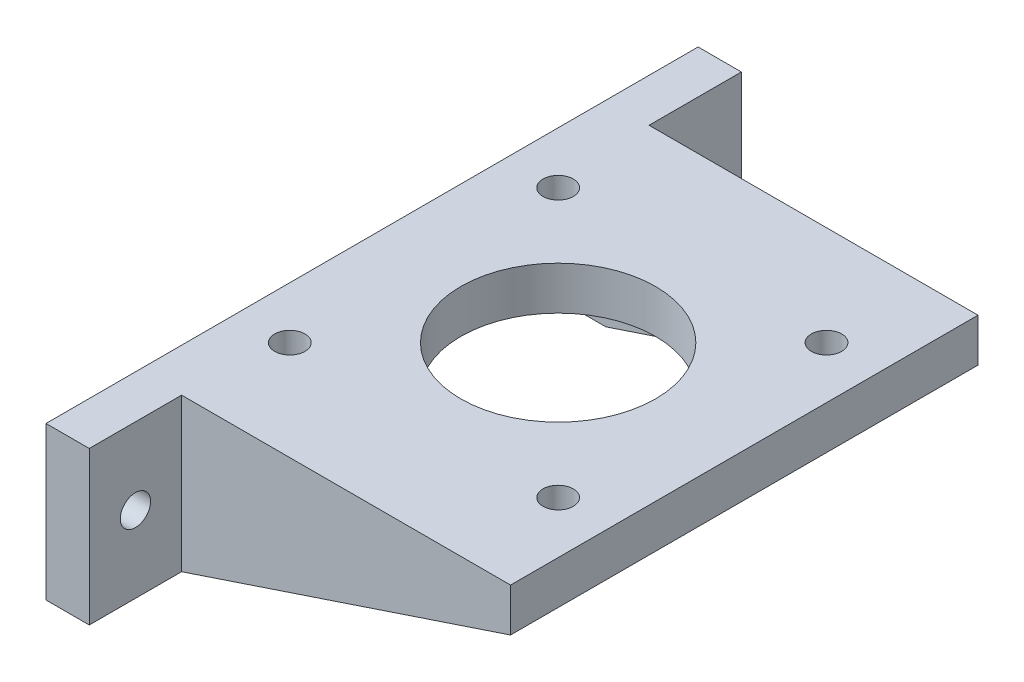
SolidWorks part; units mm, degrees
material "ABS"
ref_plane "Front Plane" through (0, 0, 0) normal (0, 0, 1) x (1, 0, 0)
ref_plane "Top Plane" through (0, 0, 0) normal (0, 1, 0) x (1, 0, 0)
ref_plane "Right Plane" through (0, 0, 0) normal (1, 0, 0) x (0, 0, -1)
sketch "Sketch1" plane through (0, 0, 0) normal (0, 0, 1) x (1, 0, 0)
  line L0 (5, 5) -> (43, 5)
  line L1 (0, 0) -> (5, 0)
  line L2 (0, 0) -> (0, 5)
  line L3 (0, 5) -> (5, 5)
  line L4 (5, 0) -> (5, 5)
  line L5 (43, 5) -> (43, 0)
  line L6 (43, 0) -> (5, 0)
  line L7 (5, 0) -> (5, -12.666)
  line L8 (5, -12.666) -> (0, -12.666)
  line L9 (0, -12.666) -> (0, 0)
  line L10 (5, -12.666) -> (43, 0)
  dimension "D1" = 5
  dimension "D2" = 5
  dimension "D3" = 43
  dimension "D4" = 12.666
extrude "Boss-Extrude1" add sketch "Sketch1" against normal blind 44 contours L1 L4 L3 L2 | L6 L5 L0 L4 region at (2.5, 2.5, 0) region at (24, 2.5, 0)
sketch "Sketch2" plane through (0, 5, 0) normal (0, 1, 0) x (1, 0, 0)
  line L3 (0, 44) -> (0, 0) construction
  line L4 (0, 0) -> (43, 0) construction
  circle A0 centre (21.5, 22) radius 11.25
  circle A1 centre (37, 37.5) radius 1.75
  circle A2 centre (6, 37.5) radius 1.75
  circle A3 centre (6, 6.5) radius 1.75
  circle A4 centre (37, 6.5) radius 1.75
  dimension "D3" = 22.5
  dimension "D4" = 3.5
  dimension "D1" = 21.5
  dimension "D2" = 22
  dimension "D5" = 15.5
  dimension "D6" = 15.5
  dimension "D7" = 2
  dimension "D8" = 2
extrude "Cut-Extrude1" cut sketch "Sketch2" against normal through all
extrude "Boss-Extrude2" add sketch "Sketch1<3>" along normal blind 5 contours L7 L10 L6 | L6 L5 L0 L4 | L1 L4 L3 L2 | L9 L8 L7 L1 region at (2.5, 2.5, 0) region at (24, 2.5, 0) region at (2.5, -6.333, 0) region at (17.6667, -4.222, 0)
sketch "Sketch1<3>" plane through (0, 0, 0) normal (0, 0, 1) x (1, 0, 0) same geometry as "Sketch1"
extrude "Boss-Extrude3" add sketch "Sketch1<4>" against normal blind 5 from vertex contours L1 L4 L3 L2 | L9 L8 L7 L1 | L7 L10 L6 | L6 L5 L0 L4 region at (2.5, 2.5, 0) region at (24, 2.5, 0) region at (2.5, -6.333, 0) region at (17.6667, -4.222, 0) starting at point (0, 5, -44)
sketch "Sketch1<4>" plane through (0, 0, 0) normal (0, 0, 1) x (1, 0, 0) same geometry as "Sketch1"
sketch "Sketch3" plane through (0, 0, 0) normal (-1, 0, 0) x (0, 0, 1)
  line L0 (5, -12.666) -> (0, -12.666) construction
  line L1 (5, 5) -> (15.666, 5)
  line L2 (5, 5) -> (5, -12.666)
  line L3 (5, -12.666) -> (15.666, -12.666)
  line L4 (15.666, 5) -> (15.666, -12.666)
  line L5 (10.333, 5) -> (10.333, -12.666) construction
  line L6 (15.666, -3.833) -> (5, -3.833) construction
  line L7 (-22, 5) -> (-22, 0) construction
  line L8 (-49, 5) -> (5, 5) construction
  line L9 (-44, 0) -> (0, 0) construction
  line L10 (-49, -12.666) -> (-59.666, -12.666)
  line L11 (-59.666, 5) -> (-59.666, -12.666)
  line L12 (-54.333, 5) -> (-54.333, -12.666) construction
  line L13 (-59.666, -3.833) -> (-49, -3.833) construction
  line L14 (-49, 5) -> (-49, -12.666)
  line L15 (-49, 5) -> (-59.666, 5)
  circle A0 centre (10.333, -3.833) radius 1.75
  circle A1 centre (-54.333, -3.833) radius 1.75
  dimension "D2" = 3.5
  dimension "D1" = 10.666
extrude "Boss-Extrude4" add sketch "Sketch3" against normal blind 5
equation "\"rod_diameter\"= 8"
equation "\"rod_hole_thickness\"= 4"
equation "\"rod_radius\"= \"rod_diameter\" / 2"
equation "\"platter_diameter\"= 320"
equation "\"platter_radius\"= \"platter_diameter\" / 2"
equation "\"extruder_mount_hole_spacing\"= 75"
equation "\"arm_rod_spacing\"= 40"
equation "\"D2@Sketch2\" = \"D1@Boss-Extrude1\" / 2"
equation "\"motor_level_rod_spacing\"= 15"
equation "\"top_frame_spacing\"= 90"
equation "\"linear_bearing_diameter\"= 15"
equation "\"z_rod_spacing\"= 75"
equation "\"platter_rod_spacing\"= 50"
equation "\"rod_nut_thickness\"= 6.5"
equation "\"rod_nut_inscribed_diameter\"= 13"
equation "\"z_height\"= 400"
equation "\"gear_pitch\"=2"
equation "\"r_gear_teeth\"= 450"
equation "\"theta_gear_teeth\"= 385"
equation "\"sheet_thickness\"=5.333"
equation "\"sheet_tab_hole_thickness\"= \"sheet_thickness\""
equation "\"sheet_tab_width\"= \"sheet_thickness\"*2"
equation "\"sheet_bolt_diameter\"= 3"
equation "\"sheet_bolt_length\"= 16"
equation "\"sheet_nut_diameter\"= 5.5"
equation "\"sheet_nut_thickness\"= 2.5"
equation "\"sheet_nut_depth\"= 10"
equation "\"bearing_outside_diameter\"= 22"
equation "\"bearing_thickness\"= 7"
equation "\"corner_part_thickness\"= \"sheet_thickness\" + \"bearing_thickness\""
equation "\"D4@Sketch1\"=\"sheet_thickness\"*2+7-\"D1@Sketch1\""
equation "\"D1@Sketch2\"= \"D3@Sketch1\" / 2"
equation "\"D1@Sketch3\"=\"sheet_thickness\"*2"
equation "\"D2@Sketch3\"=\"sheet_bolt_diameter\"+\"printed_hole_tolerance\""
equation "\"z_drive_rod_offset\"= 12"
equation "\"sheet_double_tab_width\"= 35"
equation "\"setscrew_nut_diameter\"= 6"
equation "\"setscrew_nut_thickness\"= 3"
equation "\"setscrew_bolt_diameter\"= 3"
equation "\"motor_shaft_diameter\"= 5.7"
equation "\"printed_hole_tolerance\"= 0.5"
equation "\"D4@Sketch2\"=3 +\"printed_hole_tolerance\""
equation "\"D3@Sketch2\"=22 +\"printed_hole_tolerance\""
